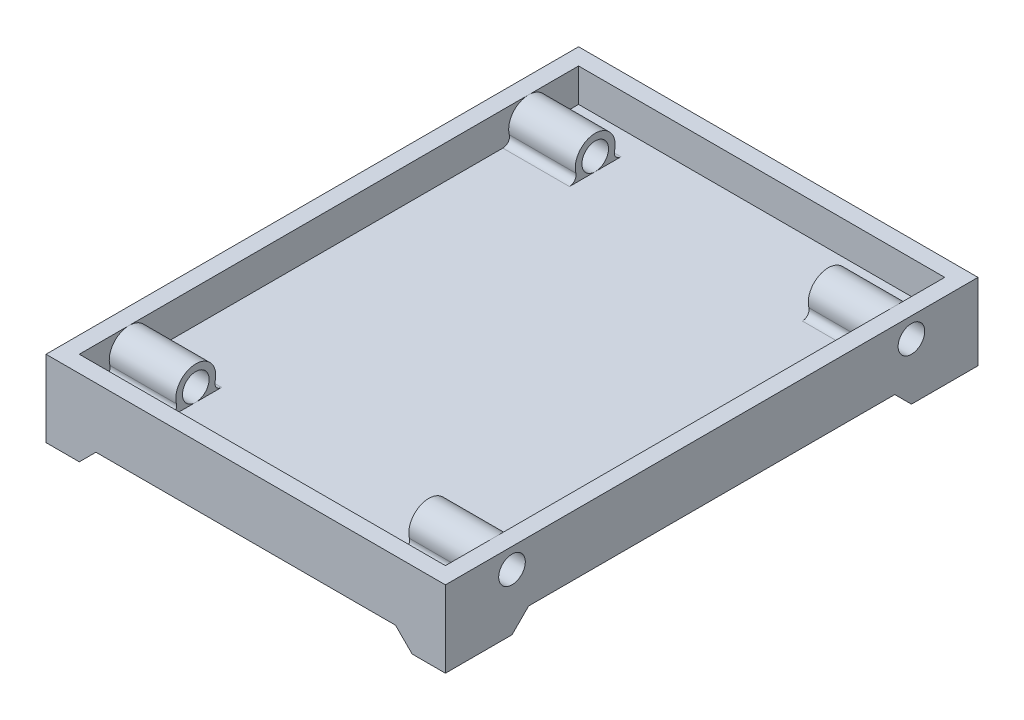
SolidWorks part; units mm, degrees
ref_plane "Front Plane" through (0, 0, 0) normal (0, 0, 1) x (1, 0, 0)
ref_plane "Top Plane" through (0, 0, 0) normal (0, 1, 0) x (1, 0, 0)
ref_plane "Right Plane" through (0, 0, 0) normal (1, 0, 0) x (0, 0, -1)
sketch "Sketch1" plane through (0, 0, 0) normal (0, 1, 0) x (1, 0, 0)
  line L1 (0, 0) -> (76.2, 0)
  line L2 (0, 0) -> (0, 101.6)
  line L3 (0, 101.6) -> (76.2, 101.6)
  line L4 (76.2, 0) -> (76.2, 101.6)
  dimension "D1" = 101.6
  dimension "D2" = 76.2
extrude "Boss-Extrude1" add sketch "Sketch1" along normal blind 5.08
sketch "Sketch4" plane through (0, 5.08, 0) normal (0, 1, 0) x (1, 0, 0)
  line L0 (0, 101.6) -> (0, 0) construction
  line L1 (3.175, 98.425) -> (73.025, 98.425)
  line L2 (3.175, 98.425) -> (3.175, 3.175)
  line L3 (3.175, 3.175) -> (73.025, 3.175)
  line L4 (73.025, 98.425) -> (73.025, 3.175)
  line L5 (76.2, 0) -> (76.2, 101.6) construction
  line L6 (0, 0) -> (76.2, 0) construction
  line L7 (76.2, 101.6) -> (0, 101.6) construction
  line L9 (0, 101.6) -> (76.2, 101.6)
  line L10 (0, 101.6) -> (0, 0)
  line L11 (0, 0) -> (76.2, 0)
  line L12 (76.2, 101.6) -> (76.2, 0)
  dimension "D1" = 3.175
  dimension "D2" = 3.175
  dimension "D3" = 3.175
  dimension "D4" = 3.175
extrude "Boss-Extrude3" add sketch "Sketch4" along normal blind 6.35
sketch "Sketch5" plane through (76.2, 0, 0) normal (1, 0, 0) x (0, 0, -1)
  line L4 (0, 0) -> (101.6, 0) construction
  line L5 (0, 11.43) -> (0, 0) construction
  line L6 (101.6, 11.43) -> (101.6, 0) construction
  circle A0 centre (12.7, 7.62) radius 2.54
  circle A1 centre (12.7, 7.62) radius 3.81
  circle A2 centre (88.9, 7.62) radius 2.54
  circle A3 centre (88.9, 7.62) radius 3.81
  point P12 (0, 0)
  dimension "D1" = 7.62
  dimension "D2" = 5.08
  dimension "D3" = 7.62
  dimension "D4" = 12.7
  dimension "D5" = 12.7
extrude "Boss-Extrude4" add sketch "Sketch5" against normal up to surface (73.025 mm away) up to face at (3.175, 8.255, -50.8)
sketch "Sketch6" plane through (76.2, 0, 0) normal (1, 0, 0) x (0, 0, -1)
  circle A0 centre (12.7, 7.62) radius 2.54
  circle A1 centre (88.9, 7.62) radius 2.54
  dimension "D1" = 5.08
extrude "Cut-Extrude2" cut sketch "Sketch6" against normal through all
sketch "Sketch7" plane through (0, 5.08, 0) normal (0, 1, 0) x (1, 0, 0)
  line L0 (73.025, 98.425) -> (3.175, 98.425) construction
  line L1 (15.875, 98.425) -> (60.325, 98.425)
  line L2 (15.875, 98.425) -> (15.875, 3.175)
  line L3 (15.875, 3.175) -> (60.325, 3.175)
  line L4 (60.325, 98.425) -> (60.325, 3.175)
  line L5 (3.175, 3.175) -> (73.025, 3.175) construction
  line L6 (3.175, 88.9) -> (3.175, 12.7) construction
  line L7 (73.025, 3.175) -> (73.025, 9.8602) construction
  dimension "D1" = 12.7
  dimension "D2" = 12.7
extrude "Cut-Extrude3" cut sketch "Sketch7" along normal through all
fillet "Fillet1" radius 1.27 8 edges at (66.675, 5.08, -9.8602) (66.675, 5.08, -15.5398) (66.675, 5.08, -91.7398) (9.525, 5.08, -91.7398) (9.525, 5.08, -9.8602) (9.525, 5.08, -86.0602) (9.525, 5.08, -15.5398) (66.675, 5.08, -86.0602)
sketch "Sketch8" plane through (0, 0, 0) normal (0, -1, 0) x (1, 0, 0)
  line L0 (0, -50.8) -> (76.2, -50.8)
  line L1 (0, 0) -> (6.35, 0)
  line L2 (0, 0) -> (0, -12.7)
  line L3 (0, -12.7) -> (6.35, -12.7)
  line L4 (6.35, 0) -> (6.35, -12.7)
  line L5 (76.2, 0) -> (69.85, 0)
  line L6 (76.2, 0) -> (76.2, -12.7)
  line L7 (76.2, -12.7) -> (69.85, -12.7)
  line L8 (69.85, 0) -> (69.85, -12.7)
  line L9 (0, -101.6) -> (0, 0) construction
  line L10 (76.2, 0) -> (76.2, -101.6) construction
  line L11 (69.85, -101.6) -> (69.85, -88.9)
  line L12 (76.2, -88.9) -> (69.85, -88.9)
  line L13 (76.2, -101.6) -> (76.2, -88.9)
  line L14 (76.2, -101.6) -> (69.85, -101.6)
  line L15 (6.35, -101.6) -> (6.35, -88.9)
  line L16 (0, -88.9) -> (6.35, -88.9)
  line L17 (0, -101.6) -> (0, -88.9)
  line L18 (0, -101.6) -> (6.35, -101.6)
  line M6 (0, 0) -> (0, -101.6)
  line M7 (0, -101.6) -> (76.2, -101.6)
  line M8 (76.2, -101.6) -> (76.2, 0)
  line M9 (76.2, 0) -> (0, 0)
  dimension "D1" = 12.7
  dimension "D2" = 6.35
extrude "Boss-Extrude5" add sketch "Sketch8" along normal blind 3.175 contours L8 L7 M9 M8 | L12 L11 M8 M7 | L16 L15 M6 M7 | L4 L3 L2 L1 region at (3.175, 0, -95.25) region at (73.025, 0, -95.25) region at (73.025, 0, -6.35)
chamfer "Chamfer1" distance 3.175 angle 45 8 edges at (69.85, 0, -95.25) (73.025, 0, -88.9) (69.85, 0, -6.35) (73.025, 0, -12.7) (3.175, 0, -12.7) (6.35, 0, -6.35) (3.175, 0, -88.9) (6.35, 0, -95.25)
